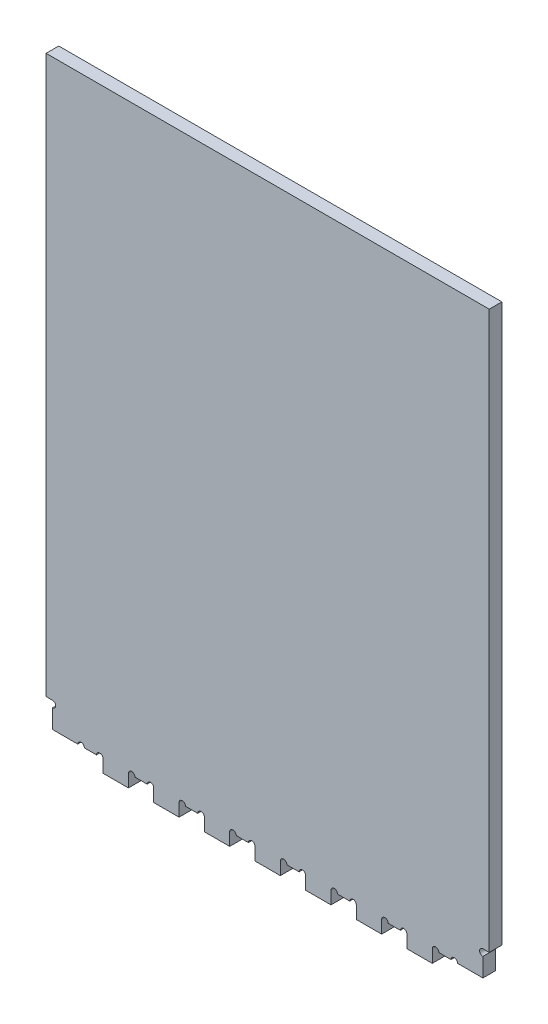
SolidWorks part; units mm, degrees
ref_plane "Front Plane" through (0, 0, 0) normal (0, 0, 1) x (1, 0, 0)
ref_plane "Top Plane" through (0, 0, 0) normal (0, 1, 0) x (1, 0, 0)
ref_plane "Right Plane" through (0, 0, 0) normal (1, 0, 0) x (0, 0, -1)
sketch "Sketch1" plane through (0, 0, 0) normal (0, 0, 1) x (1, 0, 0)
  line L1 (222.25, -304.8) -> (-222.25, -304.8)
  line L2 (222.25, -304.8) -> (222.25, 304.8)
  line L3 (222.25, 304.8) -> (-222.25, 304.8)
  line L4 (-222.25, -304.8) -> (-222.25, 304.8)
  line L5 (222.25, -304.8) -> (-222.25, 304.8) construction
  line L6 (222.25, 304.8) -> (-222.25, -304.8) construction
  line L9 (-209.55, 304.8) -> (-222.25, 304.8) construction
  point P0 (0, 0)
  dimension "D1" = 444.5
  dimension "D2" = 609.6
extrude "Boss-Extrude1" add sketch "Sketch1" along normal blind 12.7
sketch "Sketch2" plane through (0, 0, 12.7) normal (0, 0, 1) x (1, 0, 0)
  line L0 (222.25, 304.8) -> (-222.25, 304.8) construction
  line L1 (-190.5, 292.1) -> (-222.25, 292.1) construction
  line L2 (-190.5, 304.8) -> (-165.1, 304.8)
  line L3 (-190.5, 304.8) -> (-190.5, 292.1)
  line L4 (-190.5, 292.1) -> (-165.1, 292.1)
  line L5 (-165.1, 304.8) -> (-165.1, 292.1)
  line L6 (-222.25, 304.8) -> (-222.25, -304.8) construction
  circle A0 centre (-187.198, 292.1) radius 3.302
  circle A1 centre (-168.402, 292.1) radius 3.302
  line M10 (222.25, 304.8) -> (-222.25, 304.8)
  dimension "D4" = 6.604
  dimension "D5" = 6.604
  dimension "D1" = 25.4
  dimension "D2" = 12.7
  dimension "D3" = 31.75
extrude "Cut-Extrude1" cut sketch "Sketch2" against normal through all contours A1 L5 L3 A0 L4 M10 | L4 A0 | L4 A0 | L4 A1 | L4 A1 region at (-177.8, 299.0379, 12.7) region at (-187.198, 293.5014, 12.7) region at (-187.198, 290.6986, 12.7) region at (-168.402, 290.6986, 12.7) region at (-168.402, 293.5014, 12.7)
pattern_linear "LPattern1" count 8 spacing 50.8 along (1, 0, 0) of "Cut-Extrude1"
ref_plane "Plane1" through (0, 0, 0) normal (1, 0, 0) x (0, 0, -1)
ref_plane "Plane2" through (0, 0, 0) normal (0, 1, 0) x (1, 0, 0)
mirror "Mirror2" about plane through (0, 0, 0) normal (0, 1, 0) of "LPattern1"
sketch "Sketch3" plane through (0, 0, 12.7) normal (0, 0, 1) x (1, 0, 0)
  line L1 (-222.25, -304.8) -> (-215.9, -304.8)
  line L2 (-222.25, -304.8) -> (-222.25, -266.7)
  line L3 (-222.25, -266.7) -> (-215.9, -266.7)
  line L4 (-215.9, -304.8) -> (-215.9, -266.7)
  circle A0 centre (-215.9, -270.002) radius 3.302
  dimension "D3" = 6.604
  dimension "D1" = 38.1
  dimension "D2" = 6.35
extrude "Cut-Extrude2" cut sketch "Sketch3" against normal through all contours A0 L3 L2 L1 L4 | A0 region at (-219.2101, -286.9497, 12.7)
mirror "Mirror3" about plane through (0, 0, 0) normal (1, 0, 0) of "Cut-Extrude2"
sketch "Sketch4" plane through (0, 0, 12.7) normal (0, 0, 1) x (1, 0, 0)
  line L0 (222.25, -266.7) -> (222.25, 304.8) construction
  line L1 (-222.25, 304.8) -> (222.25, 304.8)
  line L2 (-222.25, 304.8) -> (-222.25, 292.1)
  line L3 (-222.25, 292.1) -> (222.25, 292.1)
  line L4 (222.25, 304.8) -> (222.25, 292.1)
  dimension "D1" = 12.7
extrude "Cut-Extrude3" cut sketch "Sketch4" against normal through all
sketch "Sketch5" plane through (0, 0, 12.7) normal (0, 0, 1) x (1, 0, 0)
  line L0 (222.25, -266.7) -> (222.25, 292.1) construction
  line L1 (-222.25, 292.1) -> (222.25, 292.1)
  line L2 (-222.25, 292.1) -> (-222.25, 273.6681)
  line L3 (-222.25, 273.6681) -> (222.25, 273.6681)
  line L4 (222.25, 292.1) -> (222.25, 273.6681)
extrude "Boss-Extrude2" add sketch "Sketch5" against normal blind 12.7
sketch "Sketch6" plane through (0, 0, 12.7) normal (0, 0, 1) x (1, 0, 0)
  line L1 (-165.1, -304.8) -> (-229.7937, -304.8)
  line L2 (-165.1, -304.8) -> (-165.1, -292.1)
  line L3 (-165.1, -292.1) -> (-229.7937, -292.1)
  line L4 (-229.7937, -304.8) -> (-229.7937, -292.1)
  dimension "D1" = 12.7
extrude "Cut-Extrude4" cut sketch "Sketch6" against normal through all
mirror "Mirror4" about plane through (0, 0, 0) normal (1, 0, 0) of "Cut-Extrude4"
